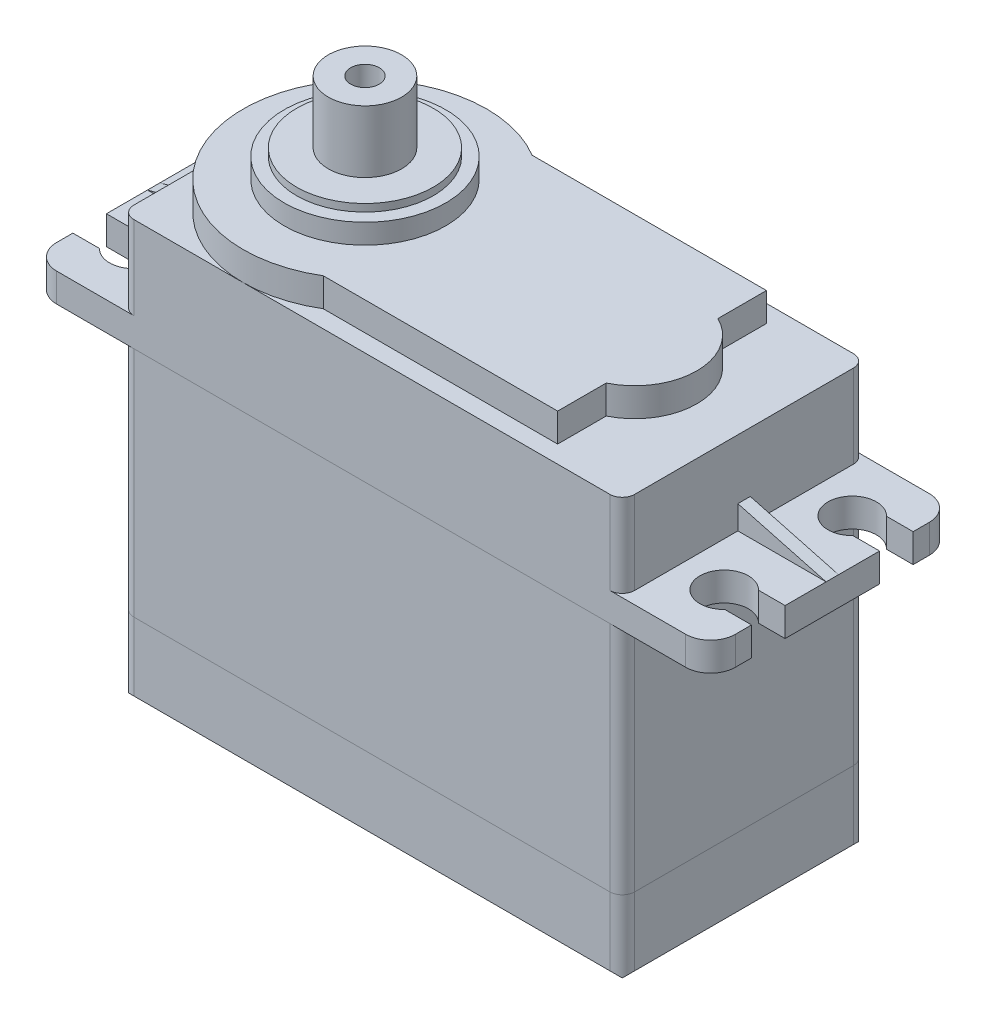
SolidWorks part; units mm, degrees
note: The reader was unsure of these and kept them because the rebuilt part matched: shared geometry of "Croquis1<3>", "Croquis1<4>", "Croquis2<3>", "Croquis2<5>", "Croquis2<6>".
ref_plane "Alzado" through (0, 0, 0) normal (0, 0, 1) x (1, 0, 0)
ref_plane "Planta" through (0, 0, 0) normal (0, 1, 0) x (1, 0, 0)
ref_plane "Vista lateral" through (0, 0, 0) normal (1, 0, 0) x (0, 0, -1)
sketch "Croquis1" plane through (0, 0, 0) normal (0, 0, 1) x (1, 0, 0)
  line L0 (47.4, -9) -> (40.3, -9)
  line L1 (0, 0) -> (40.3, 0)
  line L2 (0, 0) -> (0, -6.7)
  line L3 (0, -35) -> (40.3, -35)
  line L4 (40.3, 0) -> (40.3, -6.7)
  line L5 (47.4, -9) -> (47.4, -6.7)
  line L6 (47.4, -6.7) -> (40.3, -6.7)
  line L7 (-7.2, -9) -> (-7.2, -6.7)
  line L8 (-7.2, -6.7) -> (0, -6.7)
  line L9 (0, -9) -> (-7.2, -9)
  line L10 (0, -9) -> (0, -35)
  line L11 (40.3, -9) -> (40.3, -35)
  line L12 (40.3, -9) -> (0, -9)
  line L14 (40.3, -27.7) -> (0, -27.7)
  dimension "D1" = 40.3
  dimension "D2" = 35
  dimension "D3" = 6.7
  dimension "D4" = 7.1
  dimension "D5" = 7.2
  dimension "D6" = 2.3
  dimension "D7" = 7.3
extrude "Saliente-Extruir1" add sketch "Croquis1" against normal blind 19.6 contours L12 L0 L5 L6 L4 L1 L2 L8 L7 L9
extrude "Saliente-Extruir2" add sketch "Croquis1<3>" against normal blind 19.6 separate body contours L14 L11 L12 L10
sketch "Croquis1<3>" plane through (0, 0, 0) normal (0, 0, 1) x (1, 0, 0) same geometry as "Croquis1"
extrude "Saliente-Extruir3" add sketch "Croquis1<4>" against normal blind 19.6 separate body contours L11 L14 L10 L3
sketch "Croquis1<4>" plane through (0, 0, 0) normal (0, 0, 1) x (1, 0, 0) same geometry as "Croquis1"
fillet "Redondeo1" radius 2 4 edges at (-7.2, -7.85, -19.6) (-7.2, -7.85, 0) (47.4, -7.85, 0) (47.4, -7.85, -19.6)
fillet "Redondeo2" radius 1 4 edges at (0, -18.35, 0) (0, -18.35, -19.6) (40.3, -18.35, -19.6) (40.3, -18.35, 0)
fillet "Redondeo3" radius 1 4 edges at (0, -31.35, 0) (0, -31.35, -19.6) (40.3, -31.35, -19.6) (40.3, -31.35, 0)
fillet "Redondeo4" radius 1 4 edges at (0, -3.35, 0) (0, -3.35, -19.6) (40.3, -3.35, -19.6) (40.3, -3.35, 0)
chamfer "Chaflán1" distance 2 angle 45 1 edges at (20.15, -35, -19.6)
chamfer "Chaflán2" distance 1.8 angle 45 1 edges at (0, -35, -9.3)
chamfer "Chaflán3" distance 1.8 angle 45 2 edges at (40.3, -35, -9.3) (20.55, -35, 0) tangent propagation no
sketch "Croquis2" plane through (0, 0, 0) normal (0, 1, 0) x (1, 0, 0)
  line L0 (1, 19.6) -> (39.3, 19.6) construction
  line L2 (0, 18.6) -> (0, 1) construction
  line L3 (1, 0) -> (39.3, 0) construction
  line L4 (14.8478, 18.2) -> (33.7, 18.2)
  line L5 (33.7, 18.2) -> (33.7, 1.4) construction
  line L6 (33.7, 1.4) -> (14.8478, 1.4)
  line L7 (40.3, 18.6) -> (40.3, 1) construction
  line L8 (36.5, 13.8) -> (36.5, 5.8) construction
  line L9 (33.7, 9.8) -> (19.6, 9.8) construction
  line L10 (33.7, 18.2) -> (33.7, 14.29)
  line L11 (33.7, 5.31) -> (33.7, 1.4)
  arc A0 (14.8478, 18.2) -> (14.8478, 1.4) centre (9.8, 9.8) ccw
  circle A1 centre (9.8, 9.8) radius 2.95
  circle A2 centre (9.8, 9.8) radius 1.15
  circle A3 centre (9.8, 9.8) radius 6.5
  circle A4 centre (9.8, 9.8) radius 5.5
  arc A5 (33.7, 5.31) -> (33.7, 14.29) centre (31.5, 9.8) ccw
  point P19 (40.3, 9.8)
  dimension "D2" = 5.9
  dimension "D3" = 2.3
  dimension "D4" = 13
  dimension "D5" = 11
  dimension "D7" = 10
  dimension "D1" = 16.8
  dimension "D6" = 23.9
  dimension "D8" = 2.8
  dimension "D9" = 8
  dimension "D10" = 4
  dimension "D11" = 14.1
extrude "Saliente-Extruir4" add sketch "Croquis2" along normal blind 2.3 contours L11 A5 L10 L4 A0 L6 A3
extrude "Saliente-Extruir5" add sketch "Croquis2<3>" along normal blind 3.9 contours A3
sketch "Croquis2<3>" plane through (0, 0, 0) normal (0, 1, 0) x (1, 0, 0) same geometry as "Croquis2"
extrude "Saliente-Extruir6" add sketch "Croquis2<5>" along normal blind 4.5 contours A4
sketch "Croquis2<5>" plane through (0, 0, 0) normal (0, 1, 0) x (1, 0, 0) same geometry as "Croquis2"
extrude "Saliente-Extruir7" add sketch "Croquis2<6>" along normal blind 9.5 contours A1 | A2
sketch "Croquis2<6>" plane through (0, 0, 0) normal (0, 1, 0) x (1, 0, 0) same geometry as "Croquis2"
sketch "Croquis3" plane through (0, -6.7, 0) normal (0, 1, 0) x (1, 0, 0)
  line L0 (47.4, 9.8) -> (40.3, 9.8) construction
  line L3 (47.4, 17.6) -> (47.4, 2) construction
  line L4 (40.3, 18.6) -> (40.3, 1) construction
  line L5 (47.4, 16.3) -> (47.4, 13.6)
  line L6 (43.85, 4.65) -> (43.85, 14.95) construction
  line L7 (47.4, 13.6) -> (45.2571, 13.6)
  line L8 (47.4, 16.3) -> (45.2571, 16.3)
  line L9 (47.4, 3.3) -> (45.2571, 3.3)
  line L10 (47.4, 6) -> (45.2571, 6)
  line L11 (47.4, 3.3) -> (47.4, 6)
  line L12 (47.4, 9.8) -> (-7.2, 9.8) construction
  line L13 (-7.2, 17.6) -> (-7.2, 2) construction
  line L14 (20.1, 18.2) -> (20.1, 9.8) construction
  line L16 (14.8478, 18.2) -> (33.7, 18.2) construction
  line L17 (-3.65, 4.65) -> (-3.65, 14.95) construction
  line L18 (-7.2, 9.8) -> (-0.1, 9.8) construction
  line L19 (-7.2, 3.3) -> (-7.2, 6)
  line L20 (-7.2, 6) -> (-5.0571, 6)
  line L21 (-7.2, 3.3) -> (-5.0571, 3.3)
  line L22 (-7.2, 16.3) -> (-5.0571, 16.3)
  line L23 (-7.2, 13.6) -> (-5.0571, 13.6)
  line L24 (-7.2, 16.3) -> (-7.2, 13.6)
  arc A0 (45.2571, 3.3) -> (45.2571, 6) centre (43.85, 4.65) cw
  arc A1 (45.2571, 16.3) -> (45.2571, 13.6) centre (43.85, 14.95) ccw
  arc A2 (-5.0571, 16.3) -> (-5.0571, 13.6) centre (-3.65, 14.95) cw
  arc A3 (-5.0571, 3.3) -> (-5.0571, 6) centre (-3.65, 4.65) ccw
  point P10 (43.85, 9.8)
  point P35 (-3.65, 9.8)
  dimension "D1" = 3.9
  dimension "D2" = 10.3
  dimension "D3" = 2.7
extrude "Cortar-Extruir1" cut sketch "Croquis3" against normal up to next (2.3 mm away)
ref_plane "Plano1" through (0, 0, -9.8) normal (0, 0, 1) x (1, 0, 0)
sketch "Croquis4" plane through (0, 0, -9.8) normal (0, 0, 1) x (1, 0, 0)
  line L0 (47.4, -6.7) -> (40.3, -4.8)
  line L1 (40.3, 0) -> (40.3, -6.7) construction
  dimension "D1" = 1.9
rib "Nervio21" sketch "Croquis4" sketch "Croquis4" thickness 1 extrusion direction parallel to sketch draft on no parameters "D1"=1
sketch "Croquis5" plane through (0, 0, -9.8) normal (0, 0, 1) x (1, 0, 0)
  line L0 (-7.2, -6.7) -> (0, -4.8)
  line L1 (0, -6.7) -> (0, 0) construction
rib "Nervio24" sketch "Croquis5" sketch "Croquis5" thickness 1 extrusion direction parallel to sketch draft on no parameters "D1"=1
